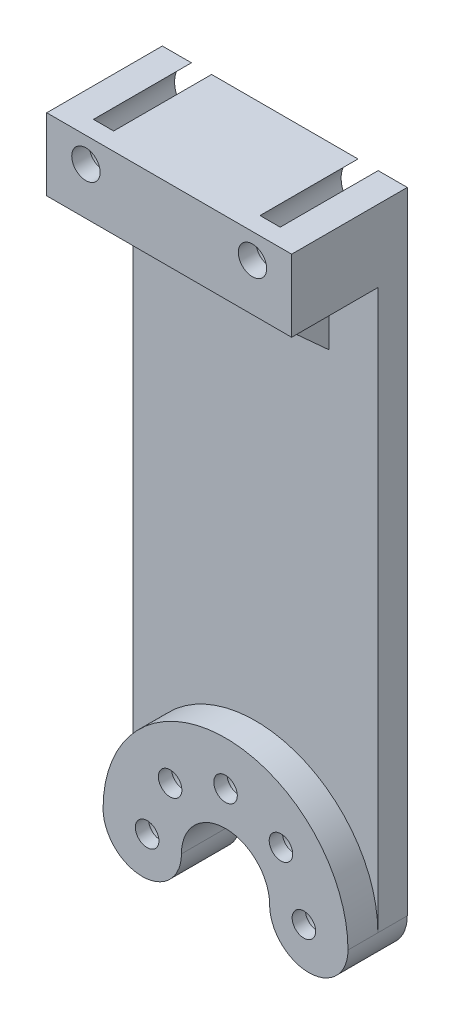
SolidWorks part; units mm, degrees
ref_plane "Plano frontal" through (0, 0, 0) normal (0, 0, 1) x (1, 0, 0)
ref_plane "Plano superior" through (0, 0, 0) normal (0, 1, 0) x (1, 0, 0)
ref_plane "Plano direito" through (0, 0, 0) normal (1, 0, 0) x (0, 0, -1)
other "Centro da massa"
sketch "Esboço1" plane through (0, 0, 0) normal (0, 0, 1) x (1, 0, 0)
  arc A0 (4.5, 0) -> (-4.5, 0) centre (0, 0) ccw
  arc A1 (12.5, 0) -> (-12.5, 0) centre (0, 0) ccw
  arc A2 (12.5, 0) -> (4.5, 0) centre (8.5, 0) cw
  arc A3 (-4.5, 0) -> (-12.5, 0) centre (-8.5, 0) cw
  arc A4 (4, 0) -> (-4, 0) centre (0, 0) ccw construction
  circle A6 centre (8.5, 61.8383) radius 1.35 construction
  dimension "D1" = 0.5
  dimension "D2" = 4
extrude "Ressalto-extrusão1" add sketch "Esboço1" against normal offset from surface (3.05 mm away) 2 offset beyond the face yes
sketch "Esboço2" plane through (0, 0, -3.05) normal (0, 0, -1) x (-1, 0, 0)
  line L1 (-12.5, 64.3883) -> (12.5, 64.3883)
  line L3 (9.2, 64.6383) -> (-9.2, 64.6383) construction
  line L6 (-12.5, 64.3883) -> (-12.5, 0)
  line L9 (12.5, 64.3883) -> (12.5, 0)
  arc A6 (4.5, 0) -> (12.5, 0) centre (8.5, 0) ccw construction
  arc A7 (-12.5, 0) -> (-4.5, 0) centre (-8.5, 0) ccw construction
  arc A8 (4.5, 0) -> (12.5, 0) centre (8.5, 0) ccw
  arc A9 (-12.5, 0) -> (-4.5, 0) centre (-8.5, 0) ccw
  arc A13 (4.5, 0) -> (-4.5, 0) centre (0, 0) ccw construction
  arc A16 (4.5, 0) -> (-4.5, 0) centre (0, 0) ccw
  dimension "D3" = 0.25
extrude "Ressalto-extrusão2" add sketch "Esboço2" along normal blind 3
sketch "Esboço4" plane through (0, 0, -6.05) normal (0, 0, -1) x (-1, 0, 0)
  line L1 (-12.5, 64.3883) -> (12.5, 64.3883)
  line L2 (-12.5, 64.3883) -> (-12.5, 57.0383)
  line L3 (-12.5, 57.0383) -> (12.5, 57.0383)
  line L4 (12.5, 64.3883) -> (12.5, 57.0383)
  line L5 (12.5, 0) -> (12.5, 64.3883) construction
  line L6 (-12.7, 59.0383) -> (12.7, 59.0383) construction
  dimension "D1" = 2
extrude "Ressalto-extrusão3" add sketch "Esboço4" against normal up to surface (11.8 mm away)
hole_wizard "Rebaixo para SHCS M2.51" positions "Sketch1" profile "Sketch2" counterbore size "M2.5" standard "Ansi Metric" end condition up to next
sketch "Sketch1" plane through (0, 0, -6.05) normal (0, 0, -1) x (-1, 0, 0)
  circle A0 centre (-8.5, 61.8383) radius 1.35 construction
  circle A1 centre (8.5, 61.8383) radius 1.35 construction
  point P0 (-8.5, 61.8383)
  point P3 (8.5, 61.8383)
sketch "Sketch2" plane through (8.5, 61.8383, -6.05) normal (1, 0, 0) x (0, 1, 0)
  line L0 (0, 0) -> (0, 11.8)
  line L1 (0, 11.8) -> (1.45, 11.8)
  line L3 (1.45, 11.8) -> (1.45, 10)
  line L4 (1.45, 10) -> (2.75, 10)
  line L5 (2.75, 10) -> (2.75, 0)
  line L7 (2.75, 0) -> (0, 0)
  line L11 (0, -6.35) -> (0, 107.95) construction
  dimension "Thru Hole Dia." = 2.9
  dimension "Thru Hole Depth" = 11.8
  dimension "C'Bore Dia." = 5.5
  dimension "C'Bore Depth" = 10
hole_wizard "Rebaixo para SHCS M21" positions "Sketch3" profile "Sketch4" counterbore size "M2" standard "Ansi Metric" end condition up to next
sketch "Sketch3" plane through (0, 0, -6.05) normal (0, 0, -1) x (-1, 0, 0)
  line L0 (0, 0) -> (-8, 0) construction
  line L1 (0, 0) -> (-5.6569, 5.6569) construction
  line L2 (0, 0) -> (0, 8) construction
  line L3 (0, 0) -> (5.6569, 5.6569) construction
  line L4 (0, 0) -> (8, 0) construction
  arc A0 (-8.8, 0) -> (-7.2, 0) centre (-8, 0) ccw construction
  point P0 (-8, 0)
  point P15 (-5.6569, 5.6569)
  point P17 (0, 8)
  point P19 (5.6569, 5.6569)
  point P21 (8, 0)
  dimension "D1" = 5
sketch "Sketch4" plane through (8, 0, -6.05) normal (1, 0, 0) x (0, 1, 0)
  line L0 (0, 0) -> (0, 6.05)
  line L1 (0, 6.05) -> (1.2, 6.05)
  line L3 (1.2, 6.05) -> (1.2, 4.7)
  line L4 (1.2, 4.7) -> (2.2, 4.7)
  line L5 (2.2, 4.7) -> (2.2, 0)
  line L7 (2.2, 0) -> (0, 0)
  line L11 (0, -6.35) -> (0, 107.95) construction
  dimension "Thru Hole Dia." = 2.4
  dimension "Thru Hole Depth" = 6.05
  dimension "C'Bore Dia." = 4.4
  dimension "C'Bore Depth" = 4.7
sketch "Esboço5" plane through (0, 0, 0) normal (1, 0, 0) x (0, 0, -1)
  line L0 (-5.75, 57.0383) -> (3.05, 49.0383)
  line L1 (3.05, 57.0383) -> (3.05, 0) construction
  line L2 (-5.75, 57.0383) -> (3.05, 57.0383) construction
  dimension "D1" = 8
rib "Nervura1" sketch "Esboço5" sketch "Esboço5" thickness 15 extrusion direction parallel to sketch draft on no parameters "D1"=15
sketch "Esboço6" plane through (0, 0, -3.05) normal (0, 0, 1) x (1, 0, 0)
  line L0 (7.5, 49.0383) -> (-7.5, 49.0383) construction
  line L1 (4.4016, 49.0383) -> (-4.5372, 49.0383)
  line L2 (4.4016, 49.0383) -> (4.4016, 57.0383)
  line L3 (4.4016, 57.0383) -> (-4.5372, 57.0383)
  line L4 (-4.5372, 49.0383) -> (-4.5372, 57.0383)
  line L5 (4.4251, 52.1001) -> (4.4021, 49.1002) construction
  line L6 (-7.5, 57.0383) -> (7.5, 57.0383) construction
  line L7 (-4.5976, 49.1693) -> (-4.5746, 52.1692) construction
extrude "Corte-extrusão1" cut sketch "Esboço6" along normal up to next
